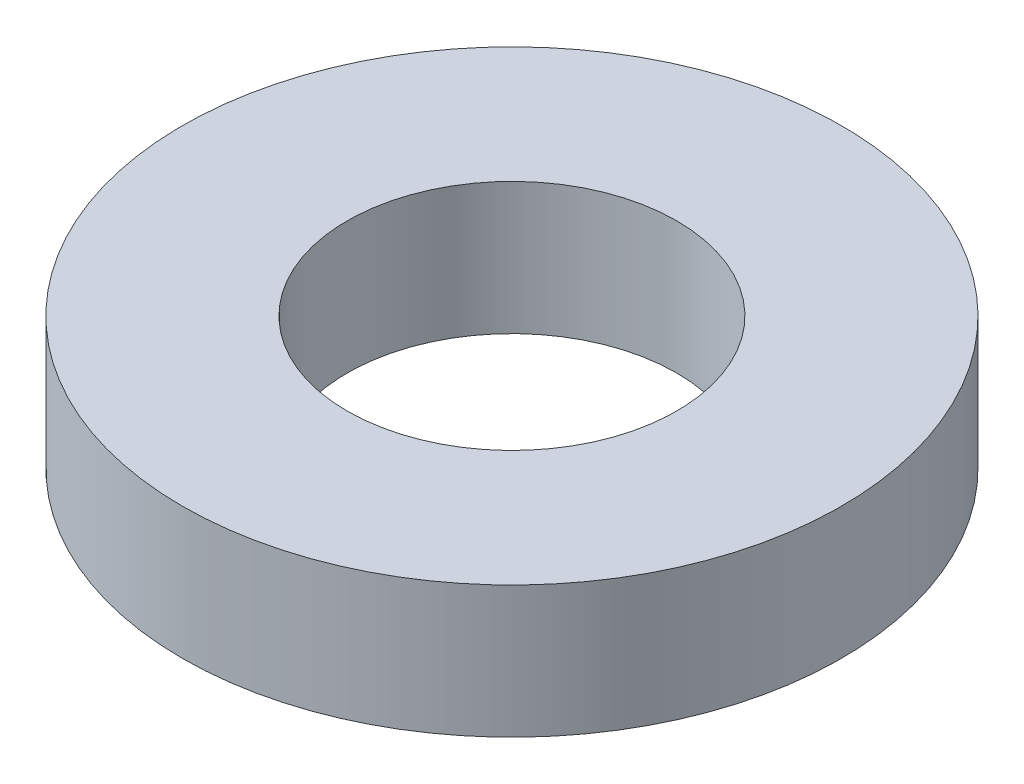
SolidWorks part; units mm, degrees
ref_plane "Front Plane" through (0, 0, 0) normal (0, 0, 1) x (1, 0, 0)
ref_plane "Top Plane" through (0, 0, 0) normal (0, 1, 0) x (1, 0, 0)
ref_plane "Right Plane" through (0, 0, 0) normal (1, 0, 0) x (0, 0, -1)
sketch "Sketch1" plane through (0, 0, 0) normal (0, 1, 0) x (1, 0, 0)
  circle A0 centre (0, 0) radius 6.35
  circle A1 centre (0, 0) radius 3.175
  dimension "D1" = 12.7
  dimension "D2" = 6.35
extrude "Boss-Extrude1" add sketch "Sketch1" along normal blind 2.54
